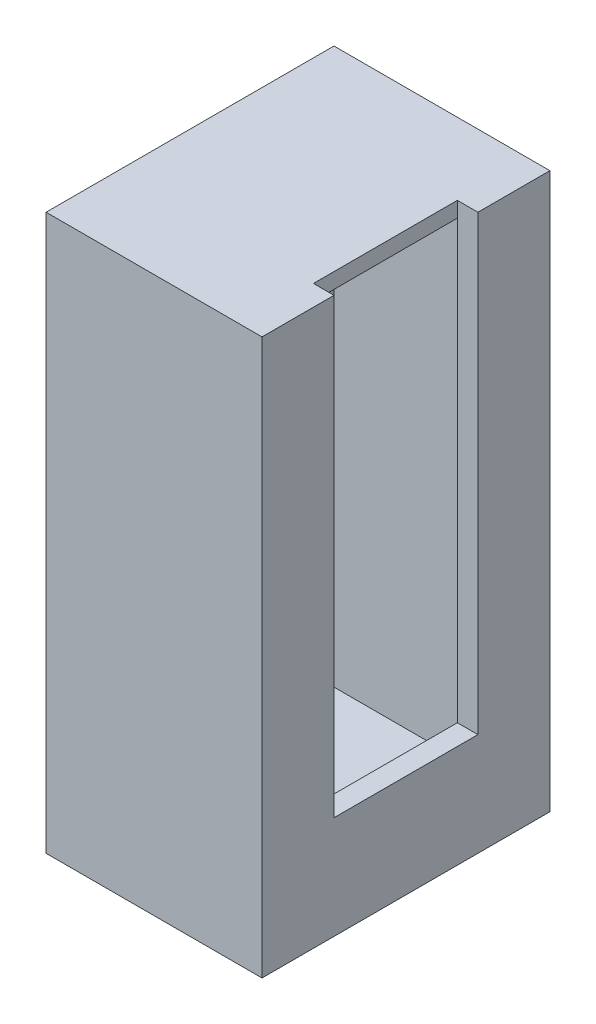
SolidWorks part; units mm, degrees
ref_plane "Alzado" through (0, 0, 0) normal (0, 0, 1) x (1, 0, 0)
ref_plane "Planta" through (0, 0, 0) normal (0, 1, 0) x (1, 0, 0)
ref_plane "Vista lateral" through (0, 0, 0) normal (1, 0, 0) x (0, 0, -1)
sketch "Croquis1" plane through (0, 0, 0) normal (0, 0, 1) x (1, 0, 0)
  line L0 (-133.35, 342.9) -> (-133.35, -342.9)
  line L1 (-133.35, -342.9) -> (133.35, -342.9)
  line L2 (133.35, -342.9) -> (133.35, 0)
  line L4 (133.35, 0) -> (133.35, 342.9)
  line L5 (133.35, 342.9) -> (-133.35, 342.9)
  line L6 (0, 342.9) -> (0, 0) construction
  line L7 (-133.35, 0) -> (0, 0) construction
  point P4 (0, 0)
  dimension "D2" = 685.8
  dimension "D4" = 266.7
extrude "Saliente-Extruir1" add sketch "Croquis1" along normal mid plane 355.6
sketch "Croquis2" plane through (133.35, 0, 0) normal (1, 0, 0) x (0, 0, -1)
  line L0 (-177.8, 342.9) -> (177.8, 342.9) construction
  line L1 (-88.9, 342.9) -> (88.9, 342.9)
  line L2 (-88.9, 342.9) -> (-88.9, -215.9)
  line L3 (-88.9, -215.9) -> (88.9, -215.9)
  line L4 (88.9, 342.9) -> (88.9, -215.9)
  line L5 (-177.8, -342.9) -> (177.8, -342.9) construction
  point P6 (0, -215.9)
  dimension "D1" = 177.8
  dimension "D2" = 127
extrude "Cortar-Extruir1" cut sketch "Croquis2" against normal blind 25.4
shell "Vaciado1" thickness 19.05 removed face at (107.95, 63.5, 0)
sketch "Croquis3" plane through (0, 342.9, 0) normal (0, 1, 0) x (1, 0, 0)
  line L0 (-44.45, 177.8) -> (-44.45, -177.8)
  line L1 (133.35, 177.8) -> (-133.35, 177.8) construction
  line L2 (133.35, -177.8) -> (-133.35, -177.8) construction
  line L3 (44.45, 177.8) -> (44.45, -177.8)
  line L4 (-133.35, -177.8) -> (-133.35, 177.8) construction
  dimension "D1" = 88.9
  dimension "D2" = 88.9
sketch "Croquis4" plane through (0, 0, 177.8) normal (0, 0, 1) x (1, 0, 0)
  line L0 (-44.45, 342.9) -> (-44.45, -342.9)
  line L1 (133.35, 342.9) -> (-133.35, 342.9) construction
  line L2 (-133.35, -342.9) -> (133.35, -342.9) construction
  line L3 (44.45, 342.9) -> (44.45, -342.9)
  line L4 (-133.35, 342.9) -> (-133.35, -342.9) construction
  dimension "D1" = 88.9
  dimension "D2" = 88.9
sketch "Croquis5" plane through (-133.35, 0, 0) normal (-1, 0, 0) x (0, 0, 1)
  line L0 (-88.9, 342.9) -> (-88.9, -342.9)
  line L1 (-177.8, 342.9) -> (177.8, 342.9) construction
  line L2 (177.8, -342.9) -> (-177.8, -342.9) construction
  line L3 (0, 342.9) -> (0, -342.9)
  line L4 (88.9, 342.9) -> (88.9, -342.9)
  line L5 (-177.8, 342.9) -> (-177.8, -342.9) construction
  dimension "D1" = 88.9
  dimension "D2" = 88.9
  dimension "D3" = 88.9
sketch "Croquis6" plane through (133.35, 0, 0) normal (1, 0, 0) x (0, 0, -1)
  line L16 (86.36, -213.36) -> (-86.36, -213.36)
  line L17 (-86.36, -213.36) -> (-86.36, 345.44)
  line L18 (-86.36, 345.44) -> (-180.34, 345.44)
  line L19 (-180.34, 345.44) -> (-180.34, -345.44)
  line L20 (-180.34, -345.44) -> (180.34, -345.44)
  line L21 (180.34, -345.44) -> (180.34, 345.44)
  line L22 (180.34, 345.44) -> (86.36, 345.44)
  line L23 (86.36, 345.44) -> (86.36, -213.36)
  line L24 (86.36, -213.36) -> (-86.36, -213.36)
  line L25 (-86.36, -213.36) -> (-86.36, 345.44)
  line L26 (-86.36, 345.44) -> (-180.34, 345.44)
  line L27 (-180.34, 345.44) -> (-180.34, -345.44)
  line L28 (-180.34, -345.44) -> (180.34, -345.44)
  line L29 (180.34, -345.44) -> (180.34, 345.44)
  line L30 (180.34, 345.44) -> (86.36, 345.44)
  line L31 (86.36, 345.44) -> (86.36, -213.36)
  dimension "D1" = 2.54
